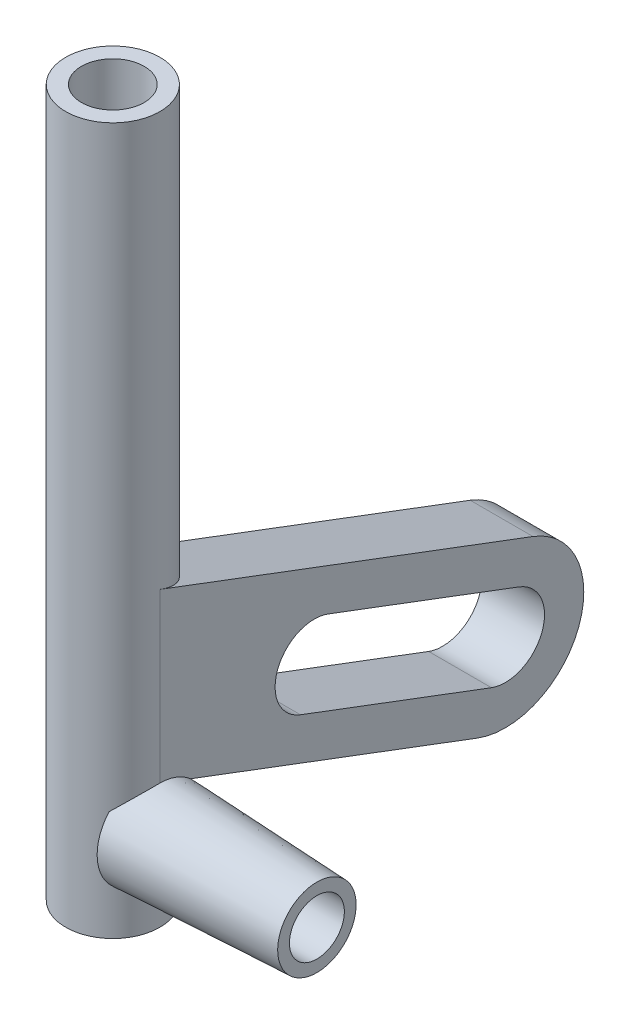
SolidWorks part; units mm, degrees
ref_plane "Спереди" through (0, 0, 0) normal (0, 0, 1) x (1, 0, 0)
ref_plane "Сверху" through (0, 0, 0) normal (0, 1, 0) x (1, 0, 0)
ref_plane "Справа" through (0, 0, 0) normal (1, 0, 0) x (0, 0, -1)
sketch "Эскиз1" plane through (0, 0, 0) normal (0, 0, 1) x (1, 0, 0)
  line L0 (0, 0) -> (0, 21.0965) construction
  line L1 (-3, 0) -> (-3, 45)
  line L2 (0, 0) -> (-2, 0) construction
  line L3 (-3, 0) -> (-2, 0)
  line L4 (-2, 0) -> (-2, 45)
  line L5 (-3, 45) -> (-2, 45)
  dimension "D1" = 6
  dimension "D2" = 4
  dimension "D3" = 45
revolve "Повернуть1" add sketch "Эскиз1" angle 360 about L0
sketch "Эскиз2" plane through (0, 0, 0) normal (0, -1, 0) x (-1, 0, 0)
  circle A0 centre (0, 0) radius 3
  dimension "D1" = 6
extrude "Бобышка-Вытянуть1" add sketch "Эскиз2" against normal blind 2
sketch "Эскиз3" plane through (0, 0, 0) normal (0, 0, 1) x (1, 0, 0)
  line L0 (-0.4212, 5) -> (23.3133, 5) construction
  line L1 (2, 2) -> (13, 2.5)
  line L2 (2, 2) -> (2, 3.25)
  line L6 (13, 2.5) -> (13, 3.25)
  line L7 (13, 3.25) -> (2, 3.25)
  dimension "D1" = 6
  dimension "D2" = 3.5
  dimension "D3" = 5
  dimension "D4" = 11
  dimension "D5" = 2
  dimension "D6" = 2
revolve "Повернуть2" add sketch "Эскиз3" angle 360 about L0
sketch "Эскиз4" plane through (13, 0, 0) normal (1, 0, 0) x (0, 0, -1)
  circle A0 centre (0, 5) radius 1.75
extrude "Вырез-Вытянуть1" cut sketch "Эскиз4" against normal blind 13
ref_plane "Плоскость1" through (3, 0, 0) normal (1, 0, 0) x (0, 0, -1)
sketch "Эскиз5" plane through (3, 0, 0) normal (1, 0, 0) x (0, 0, -1)
  line L0 (0, 18.6423) -> (23.7646, 9.6783)
  line L1 (0, 7.9545) -> (20.2354, 0.3217)
  line L2 (23.7646, 9.6783) -> (20.2354, 0.3217) construction
  line L3 (0, 7.9545) -> (0, 18.6423)
  line L4 (0, 0) -> (37.9137, 0) construction
  line L5 (0, 0) -> (0, 7.9545) construction
  line L6 (10.7189, 11.9272) -> (22.8823, 7.3391)
  line L7 (8.9542, 7.2489) -> (21.1177, 2.6609)
  line L9 (2.5, 9.6835) -> (2.5, 15.0274) construction
  line L10 (22, 5) -> (9.8365, 9.5881) construction
  line L12 (2.5, 9.6835) -> (21.1177, 2.6609) construction
  line L13 (2.5, 15.0274) -> (22.8823, 7.3391) construction
  arc A0 (20.2354, 0.3217) -> (23.7646, 9.6783) centre (22, 5) ccw
  arc A1 (21.1177, 2.6609) -> (22.8823, 7.3391) centre (22, 5) ccw
  arc A2 (10.7189, 11.9272) -> (8.9542, 7.2489) centre (9.8365, 9.5881) ccw
  spline S0 degree 3 poles (-2.2361, 7) (-2.1103, 7.1311) (-1.9701, 7.2544) (-1.6563, 7.4811) (-1.48, 7.5857) (-1.0994, 7.7602) (-0.8929, 7.8313) (-0.4561, 7.9289) (-0.2324, 7.9543) (0.1116, 7.9547) (0.2273, 7.9483) (0.4526, 7.9233) (0.5634, 7.9048) (0.8905, 7.832) (1.0985, 7.7606) (1.4803, 7.5856) (1.6563, 7.4811) (1.97, 7.2545) (2.1102, 7.1311) (2.2361, 7) knots 0 0 0 0 0.125 0.125 0.25 0.25 0.375 0.375 0.5 0.5 0.5625 0.5625 0.625 0.625 0.75 0.75 0.875 0.875 1 1 1 1 construction
  dimension "D2" = 27
  dimension "D4" = 5
  dimension "D5" = 18
  dimension "D1" = 10
  dimension "D3" = 2.5
extrude "Бобышка-Вытянуть2" add sketch "Эскиз5" against normal blind 4
sketch "Эскиз6" plane through (0, 45, 0) normal (0, 1, 0) x (1, 0, 0)
  circle A0 centre (0, 0) radius 2
extrude "Вырез-Вытянуть2" cut sketch "Эскиз6" against normal blind 43
